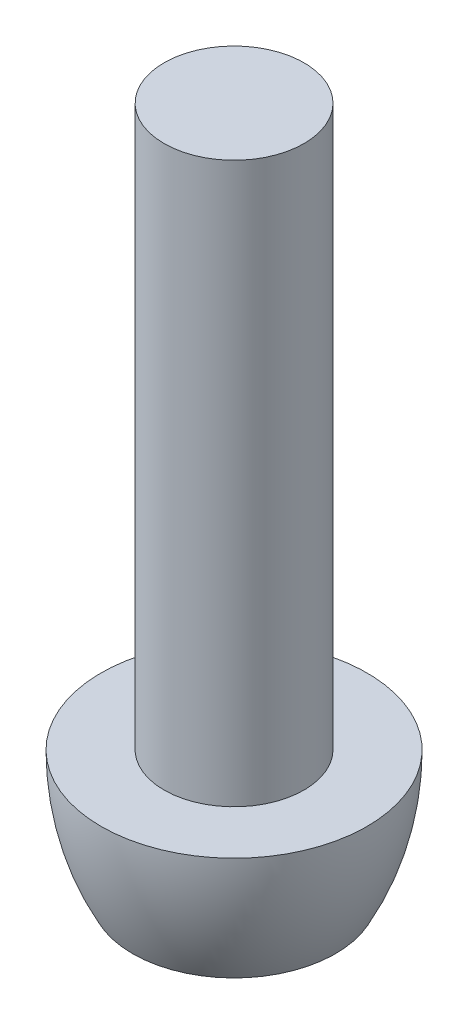
SolidWorks part; units mm, degrees
note: '?' marks a value the reader was unsure of. The reader was unsure of these and kept them because the rebuilt part matched: shared geometry of "草图1<3>".
ref_plane "前视基准面" through (0, 0, 0) normal (0, 0, 1) x (1, 0, 0)
ref_plane "上视基准面" through (0, 0, 0) normal (0, 1, 0) x (1, 0, 0)
ref_plane "右视基准面" through (0, 0, 0) normal (1, 0, 0) x (0, 0, -1)
sketch "草图1" plane through (0, 0, 0) normal (0, 1, 0) x (1, 0, 0)
  line L0 (1, 0) -> (1.9, 0) construction
  circle A0 centre (0, 0) radius 1
  circle A1 centre (0, 0) radius 1.9
  circle A2 centre (0, 0) radius 1.45 construction
  point P7 (1.45, 0)
  dimension "d" = 2
  dimension "D " = 3.8
extrude "公称长度" add sketch "草图1" along normal blind 8 contours A0
cosmetic thread "装饰螺纹线1" parameters "D2"=0.0001
extrude "头部高" add sketch "草图1<3>" against normal blind 1.8 contours A0 | A1 A0
sketch "草图1<3>" plane through (0, 0, 0) normal (0, 1, 0) x (1, 0, 0) same geometry as "草图1"
sketch "草图2" plane through (0, 0, 0) normal (0, 0, 1) x (1, 0, 0)
  line L0 (1.45, 0) -> (-1.45, 0) construction
  line L2 (-1.9, -1.8) -> (1.9, -1.8) construction
  line L6 (1.9, 0) -> (-1.9, 0) construction
  line L7 (-1.9, 0) -> (-1.9, -1.8)
  line L8 (-1.9, -1.8) -> (-1.45, -1.8)
  arc A1 (-1.9, 0) -> (-1.45, -1.8) centre (1.925, 0) ccw
  point P0 (-1.45, 0)
ref_axis "基准轴1" through (0, 8, 0) along (0, -1, 0)?
revolve "切除-旋转1" cut sketch "草图2" angle 360
sketch "草图3" plane through (0, -1.8, 0) normal (0, -1, 0) x (1, 0, 0)
  line L1 (-0.2887, -0.5) -> (0.2887, -0.5)
  line L2 (0.2887, -0.5) -> (0.5774, 0)
  line L3 (0.5774, 0) -> (0.2887, 0.5)
  line L4 (0.2887, 0.5) -> (-0.2887, 0.5)
  line L5 (-0.2887, 0.5) -> (-0.5774, 0)
  line L6 (-0.5774, 0) -> (-0.2887, -0.5)
  circle A0 centre (0, 0) radius 0.5 construction
  dimension "D1" = 1
extrude "切除-拉伸1" cut sketch "草图3" against normal blind 0.6
